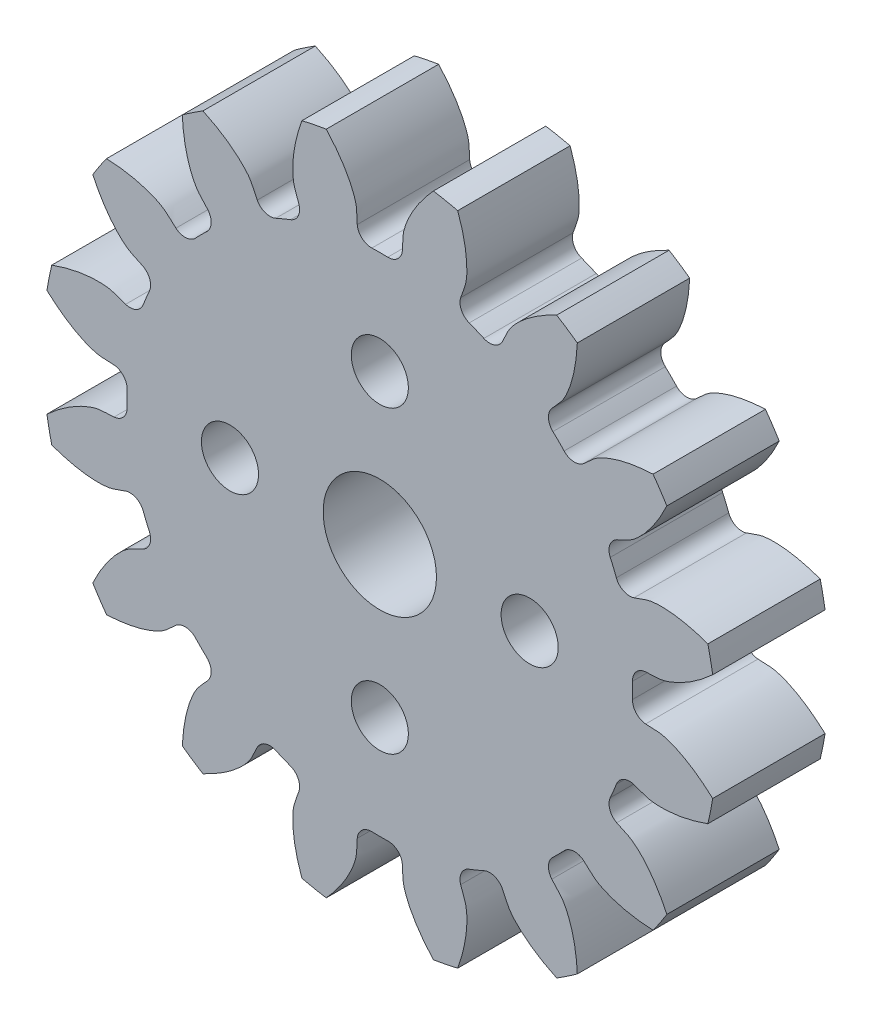
SolidWorks part; units mm, degrees
material "Thornel Mat VMA"
ref_plane "前视基准面" through (0, 0, 0) normal (0, 0, 1) x (1, 0, 0)
ref_plane "上视基准面" through (0, 0, 0) normal (0, 1, 0) x (1, 0, 0)
ref_plane "右视基准面" through (0, 0, 0) normal (1, 0, 0) x (0, 0, -1)
other "Configuration Table"
ref_axis "Axis1" through (0, 0, -88.99) along (0, 0, 1)
sketch "草图1" plane through (0, 0, 0) normal (0, 0, 1) x (1, 0, 0)
  circle A0 centre (0, 0) radius 18
extrude "LaShenA" add sketch "草图1" along normal blind 6
sketch "SketchA" plane through (0, 0, 6) normal (0, 0, 1) x (1, 0, 0)
  line L0 (0, 0) -> (0, 18) construction
  arc A0 (0.4232, 13.4934) -> (-0.4232, 13.4934) centre (0, 0) ccw
  arc A1 (3.858, 18.7275) -> (-3.858, 18.7275) centre (0, 0) ccw
  arc A2 (-0.4232, 13.4934) -> (-1.2044, 14.1898) centre (-0.447, 14.253) cw
  arc A3 (1.2044, 14.1898) -> (0.4232, 13.4934) centre (0.447, 14.253) cw
  circle A4 centre (0, 0) radius 15.0351 construction
  circle A5 centre (0, 0) radius 18 construction
  circle A6 centre (0, 0) radius 13.5 construction
  circle A7 centre (0, 0) radius 16 construction
  spline S0 degree 3 poles (1.2044, 14.1898) (1.2266, 14.4552) (1.2138, 14.7739) (1.2737, 15.1106) (1.2991, 15.2114) (1.3214, 15.2911) (1.3499, 15.3823) (1.3851, 15.4846) (1.4278, 15.5978) (1.4786, 15.7214) (1.5382, 15.8552) (1.6071, 15.9987) (1.686, 16.1514) (1.7754, 16.3129) (1.876, 16.4827) (1.9884, 16.6603) (2.1129, 16.8451) (2.2502, 17.0365) (2.4007, 17.234) (2.5649, 17.4369) (2.7432, 17.6446) (2.9361, 17.8564) (3.1439, 18.0718) (3.4474, 18.3685) (3.6895, 18.585) (3.858, 18.7275) knots 0.122308 0.122308 0.122308 0.122308 0.250611 0.276296 0.287604 0.300968 0.316388 0.333864 0.353395 0.374983 0.398627 0.424327 0.452082 0.481894 0.513762 0.547685 0.583665 0.6217 0.661792 0.703939 0.748143 0.794402 0.842718 0.893089 1 1 1 1
  spline S1 degree 3 poles (-1.2044, 14.1898) (-1.2266, 14.4552) (-1.2138, 14.7739) (-1.2737, 15.1106) (-1.2991, 15.2114) (-1.3214, 15.2911) (-1.3499, 15.3823) (-1.3851, 15.4846) (-1.4278, 15.5978) (-1.4786, 15.7214) (-1.5382, 15.8552) (-1.6071, 15.9987) (-1.686, 16.1514) (-1.7754, 16.3129) (-1.876, 16.4827) (-1.9884, 16.6603) (-2.1129, 16.8451) (-2.2502, 17.0365) (-2.4007, 17.234) (-2.5649, 17.4369) (-2.7432, 17.6446) (-2.9361, 17.8564) (-3.1439, 18.0718) (-3.4474, 18.3685) (-3.6895, 18.585) (-3.858, 18.7275) knots 0.122308 0.122308 0.122308 0.122308 0.250611 0.276296 0.287604 0.300968 0.316388 0.333864 0.353395 0.374983 0.398627 0.424327 0.452082 0.481894 0.513762 0.547685 0.583665 0.6217 0.661792 0.703939 0.748143 0.794402 0.842718 0.893089 1 1 1 1
  dimension "D1" = 0.76
  dimension "Db" = 30.0702
  dimension "Da" = 36
  dimension "Df" = 27
  dimension "Dn" = 32
extrude "Cut-ExtrudeA" cut sketch "SketchA" against normal blind 30
pattern_circular "www.KYTool.cn" count 16 over 360 about axis through (0, 0, -88.99) along (0, 0, 1) of "Cut-ExtrudeA"
sketch "草图3" plane through (0, 0, 6) normal (0, 0, 1) x (1, 0, 0)
  circle A0 centre (0, 0) radius 8
  dimension "D1" = 16
sketch "草图4" plane through (0, 0, 6) normal (0, 0, 1) x (1, 0, 0)
  circle A0 centre (0, 0) radius 3.8023
sketch "草图5" plane through (0, 0, 6) normal (0, 0, 1) x (1, 0, 0)
  circle A0 centre (0, 0) radius 3.025
  dimension "D1" = 6.05
extrude "切除-拉伸2" cut sketch "草图5" against normal blind 10
sketch "草图6" plane through (0, 0, 0) normal (0, 0, -1) x (-1, 0, 0)
  circle A0 centre (0, 0) radius 8 construction
  circle A1 centre (0, 8) radius 1.525
  circle A2 centre (0, -8) radius 1.525
  circle A3 centre (8, 0) radius 1.525
  circle A4 centre (-8, 0) radius 1.525
  dimension "D1" = 16
  dimension "D2" = 3.05
extrude "切除-拉伸3" cut sketch "草图6" against normal blind 10
